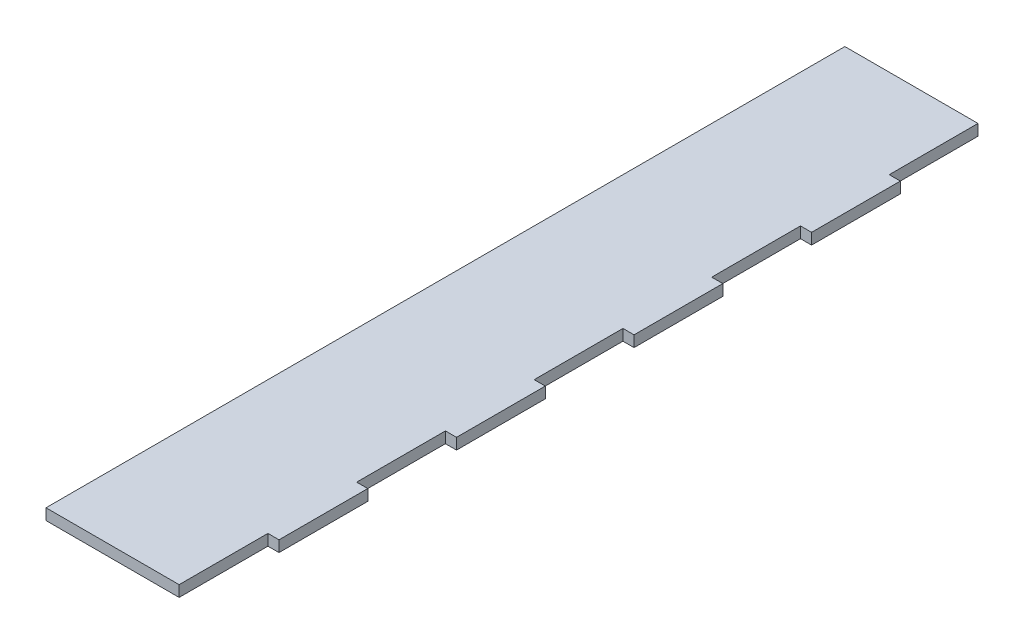
SolidWorks part; units mm, degrees
ref_plane "Front Plane" through (0, 0, 0) normal (0, 0, 1) x (1, 0, 0)
ref_plane "Top Plane" through (0, 0, 0) normal (0, 1, 0) x (1, 0, 0)
ref_plane "Right Plane" through (0, 0, 0) normal (1, 0, 0) x (0, 0, -1)
sketch "Sketch1" plane through (0, 0, 0) normal (0, 0, 1) x (1, 0, 0)
  line L1 (-38.1, -38.1) -> (38.1, -38.1) construction
  line L2 (-38.1, -38.1) -> (-38.1, 38.1) construction
  line L3 (-38.1, 38.1) -> (38.1, 38.1) construction
  line L4 (38.1, -38.1) -> (38.1, 38.1) construction
  line L5 (-38.1, -38.1) -> (38.1, 38.1) construction
  line L6 (-38.1, 38.1) -> (38.1, -38.1) construction
  line L7 (-38.1, -38.1) -> (38.1, -38.1)
  line L8 (-38.1, -38.1) -> (-38.1, -44.45)
  line L9 (-38.1, -44.45) -> (38.1, -44.45)
  line L10 (38.1, -38.1) -> (38.1, -44.45)
  point P0 (0, 0)
  dimension "D1" = 76.2
  dimension "D2" = 6.35
extrude "Boss-Extrude1" add sketch "Sketch1" along normal blind 457.2
sketch "Sketch2" plane through (38.1, 0, 0) normal (1, 0, 0) x (0, 0, -1)
  line L0 (-457.2, -44.45) -> (0, -44.45) construction
  line L1 (-406.4, -44.45) -> (-355.6, -44.45)
  line L2 (-406.4, -44.45) -> (-406.4, -38.1)
  line L3 (-406.4, -38.1) -> (-355.6, -38.1)
  line L4 (-355.6, -44.45) -> (-355.6, -38.1)
  line L5 (-406.4, -44.45) -> (-406.4, -38.1) construction
  line L6 (-355.6, -38.1) -> (-355.6, -44.45) construction
  line L7 (-457.2, -38.1) -> (0, -38.1) construction
  line L8 (-304.8, -44.45) -> (-304.8, -38.1) construction
  line L9 (-304.8, -44.45) -> (-254, -44.45)
  line L10 (-304.8, -44.45) -> (-304.8, -38.1)
  line L11 (-304.8, -38.1) -> (-254, -38.1)
  line L12 (-254, -44.45) -> (-254, -38.1)
  line L13 (-203.2, -44.45) -> (-152.4, -44.45)
  line L14 (-203.2, -44.45) -> (-203.2, -38.1)
  line L15 (-203.2, -38.1) -> (-152.4, -38.1)
  line L16 (-152.4, -44.45) -> (-152.4, -38.1)
  line L17 (-101.6, -44.45) -> (-50.8, -44.45)
  line L18 (-101.6, -44.45) -> (-101.6, -38.1)
  line L19 (-101.6, -38.1) -> (-50.8, -38.1)
  line L20 (-50.8, -44.45) -> (-50.8, -38.1)
  line L21 (-254, -38.1) -> (-254, -44.45) construction
  line L22 (-203.2, -44.45) -> (-203.2, -38.1) construction
  line L23 (-152.4, -38.1) -> (-152.4, -44.45) construction
  line L24 (-101.6, -44.45) -> (-101.6, -38.1) construction
  line L25 (-50.8, -38.1) -> (-50.8, -44.45) construction
extrude "Boss-Extrude2" add sketch "Sketch2" along normal up to surface (6.35 mm away) up to face at (38.1, -41.275, 228.6)
